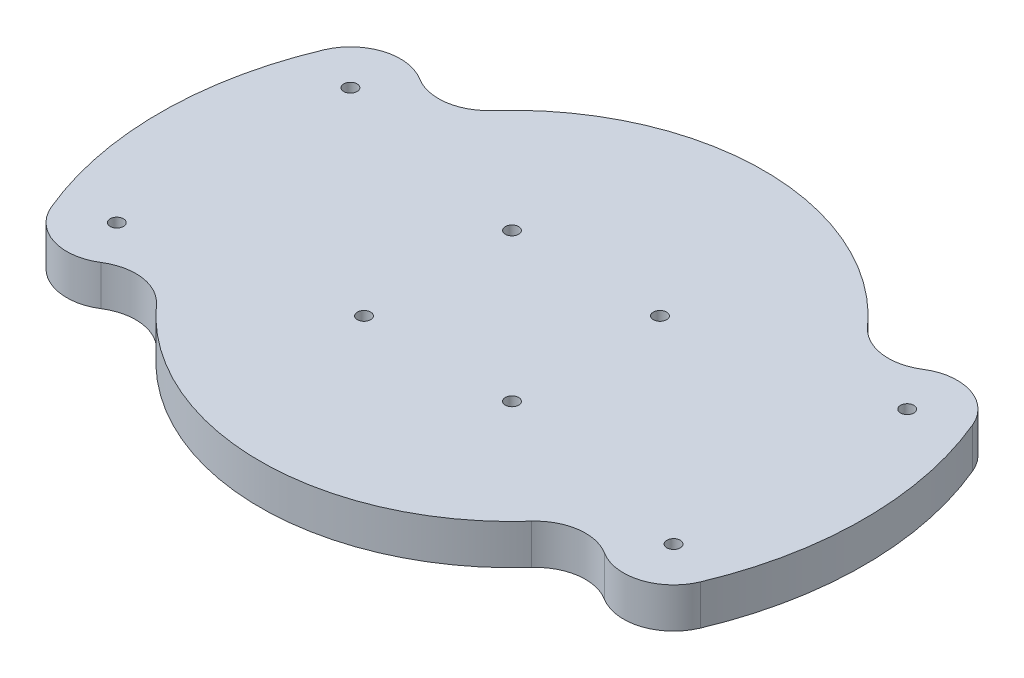
SolidWorks part; units mm, degrees
ref_plane "Front Plane" through (0, 0, 0) normal (0, 0, 1) x (1, 0, 0)
ref_plane "Top Plane" through (0, 0, 0) normal (0, 1, 0) x (1, 0, 0)
ref_plane "Right Plane" through (0, 0, 0) normal (1, 0, 0) x (0, 0, -1)
sketch "Sketch1" plane through (0, 0, 0) normal (0, 1, 0) x (1, 0, 0)
  line L0 (0, 42.5788) -> (0, -44.3324) construction
  line L1 (-11.0839, 11.0839) -> (0, 0) construction
  line L2 (41.7019, 17.5) -> (41.7019, -17.5) construction
  line L3 (31.8836, 20.1646) -> (44.561, 28.1823)
  line L4 (-64.518, 0) -> (71.4295, 0) construction
  line L5 (0, 0) -> (44.561, 28.1823) construction
  line L6 (31.8836, -20.1646) -> (44.561, -28.1823)
  line L7 (-31.8836, -20.1646) -> (-44.561, -28.1823)
  line L8 (-31.8836, 20.1646) -> (-44.561, 28.1823)
  circle A0 centre (0, 0) radius 37.725 construction
  circle A1 centre (-11.0839, 11.0839) radius 1
  circle A2 centre (11.0839, 11.0839) radius 1
  circle A3 centre (11.0839, -11.0839) radius 1
  circle A4 centre (-11.0839, -11.0839) radius 1
  circle A9 centre (41.7019, 17.5) radius 1
  circle A10 centre (41.7019, -17.5) radius 1
  circle A11 centre (0, 0) radius 52.725 construction
  arc A12 (44.561, 28.1823) -> (44.561, -28.1823) centre (0, 0) cw
  arc A13 (-31.8836, 20.1646) -> (31.8836, 20.1646) centre (0, 0) cw
  arc A14 (-31.8836, -20.1646) -> (31.8836, -20.1646) centre (0, 0) ccw
  circle A15 centre (-41.7019, 17.5) radius 1
  circle A16 centre (-41.7019, -17.5) radius 1
  arc A17 (-44.561, 28.1823) -> (-44.561, -28.1823) centre (0, 0) ccw
  point P18 (0, 0)
  point P23 (0, 0)
  point P27 (41.7019, 0)
  dimension "D1" = 75.45
  dimension "D3" = 2
  dimension "D6" = 15
  dimension "D9" = 2
  dimension "D2" = 15.675
  dimension "D4" = 45
  dimension "D7" = 45.225
  dimension "D8" = 35
  dimension "D10" = 7.5
  dimension "D5" = 4
extrude "Boss-Extrude1" add sketch "Sketch1" along normal blind 6
fillet "Fillet1" radius 7.5 8 edges at (44.561, 3, 28.1823) (31.8836, 3, 20.1646) (-44.561, 3, 28.1823) (-31.8836, 3, 20.1646) (44.561, 3, -28.1823) (31.8836, 3, -20.1646) (-44.561, 3, -28.1823) (-31.8836, 3, -20.1646)
hole_wizard "CSK for M2 Flat Head Machine Screw2" [suppressed] positions "Sketch5" profile "Sketch4" countersink size "M5" standard "ANSI Metric"
sketch "Sketch5" plane through (0, 6, 0) normal (0, 1, 0) x (1, 0, 0)
  point P0 (-11.0839, 11.0839)
  point P3 (11.0839, 11.0839)
  point P6 (11.0839, -11.0839)
  point P9 (-11.0839, -11.0839)
sketch "Sketch4" plane through (-11.0839, 6, -11.0839) normal (1, 0, 0) x (0, 0, 1)
  line L0 (0, 0) -> (0, 6)
  line L1 (0, 6) -> (2.75, 6)
  line L2 (2.75, 6) -> (2.75, 2.45)
  line L3 (2.75, 2.45) -> (5.2, 0)
  line L5 (5.2, 0) -> (0, 0)
  line L6 (-2.75, 2.45) -> (-5.2, 0) construction
  line L11 (0, -6.35) -> (0, 107.95) construction
  dimension "Thru Hole Dia." = 5.5
  dimension "Thru Hole Depth" = 6
  dimension "Near C'Sink Dia." = 10.4
  dimension "Near C'Sink Angle" = 90
equation "\"D7@Sketch1\"=\"D1@Sketch1\"/2+\"D6@Sketch1\"/2"
